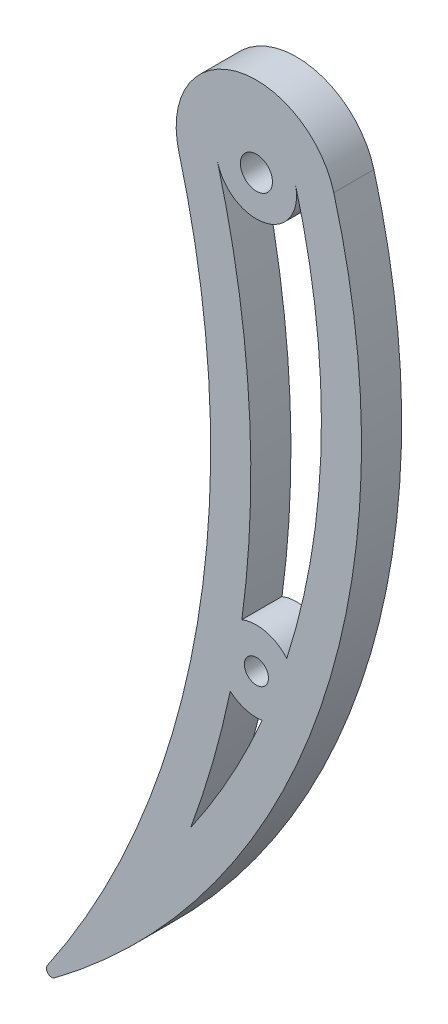
SolidWorks part; units mm, degrees
material "1060 Alloy"
ref_plane "Front Plane" through (0, 0, 0) normal (0, 0, 1) x (1, 0, 0)
ref_plane "Top Plane" through (0, 0, 0) normal (0, 1, 0) x (1, 0, 0)
ref_plane "Right Plane" through (0, 0, 0) normal (1, 0, 0) x (0, 0, -1)
sketch "Sketch1" plane through (0, 0, 0) normal (0, 0, 1) x (1, 0, 0)
  line L0 (5.1445, 48.6362) -> (5.1445, -5.1638)
  line L1 (-21.7555, -51.7438) -> (5.1445, -5.1638)
  line L2 (-17.4256, -54.2443) -> (10.1445, -6.5038)
  line L3 (0.1445, 48.6362) -> (0.1445, -5.1638)
  line L4 (10.1445, 48.6362) -> (10.1445, -5.1638)
  line L5 (10.1445, 48.6362) -> (10.1445, -6.5038)
  line L6 (-26.0853, -49.2433) -> (0.1445, -3.8237)
  line L7 (0.1445, 48.6362) -> (0.1445, -3.8237)
  circle A0 centre (5.1445, 48.6362) radius 2
  circle A1 centre (-21.7555, -51.7438) radius 2
  arc A2 (-17.4256, -54.2443) -> (-26.0853, -49.2433) centre (-21.7555, -51.7438) cw
  arc A3 (0.1445, 48.6362) -> (10.1445, 48.6362) centre (5.1445, 48.6362) cw
  circle A4 centre (5.1445, -5.1638) radius 1.5
  arc A5 (10.1445, 48.6362) -> (0.1445, 48.6362) centre (5.1445, 48.6362) ccw
  circle A6 centre (-95.2141, 21.7362) radius 99.0802
  arc A7 (0.1445, -5.1638) -> (10.1445, -5.1638) centre (5.1445, -5.1638) ccw
  circle A8 centre (5.9967, -2.4738) radius 104.0661
  circle A9 centre (-95.2141, 21.7362) radius 108.8802
  dimension "D2" = 4
  dimension "D3" = 4
  dimension "D1" = 3
extrude "Extrude1" add sketch "Sketch1" along normal blind 5 contours A7 L3 L6 A2 L2 A1 | A2 A9 L2 | L5 A9 A3 L4 | A3 A9 A6 A7 A4 A0 L4 | L2 A9 A7 | A7 A9 L5 region at (6.16, 21.4167, 0) region at (-9.5246, -32.956, 0) region at (-2.7557, -31.6611, 0) region at (9.716, -7.2082, 0) region at (10.1257, -5.6796, 0) region at (11.555, 21.7384, 0)
sketch "Sketch3" plane through (0, 0, 0) normal (0, 0, -1) x (-1, 0, 0)
  circle A0 centre (-5.1445, -5.1638) radius 7.5 construction
  arc A1 (4.5159, 46.0523) -> (-14.7839, 51.2976) centre (-5.1445, 48.6362) ccw
  arc A2 (19.9834, -50.8165) -> (-14.7839, 51.2976) centre (77.6238, 25.7843) cw
  circle A3 centre (21.7555, -51.7438) radius 2 construction
  arc A4 (20.9096, -49.9314) -> (4.5159, 46.0523) centre (117.2126, 15.9087) cw
  arc A5 (19.9834, -50.8165) -> (20.9096, -49.9314) centre (20.3737, -50.2978) ccw
  arc M1 (-9.8312, 50.3783) -> (18.5686, -55.5965) centre (95.2141, 21.7362) ccw
  arc M2 (18.5686, -55.5965) -> (26.0853, -49.2433) centre (21.7555, -51.7438) ccw
  arc M3 (26.0853, -49.2433) -> (-0.1445, 48.6362) centre (95.2141, 21.7362) cw
  arc M4 (-0.1445, 48.6362) -> (-9.8312, 50.3783) centre (-5.1445, 48.6362) ccw
  circle M5 centre (21.7555, -51.7438) radius 2
  dimension "D1" = 15
  dimension "D2" = 20
extrude "Cut-Extrude1" cut sketch "Sketch3" against normal blind 10 contours A4 A2 M5 M1 M2 M3 region at (-15.9387, -38.3925, 0)
extrude "Boss-Extrude1" add sketch "Sketch3<3>" against normal blind 5 contours A4 A1 A2 M3 M1 M4 | A5 M5 region at (0.2001, 9.8384, 0) region at (-20.5766, -50.5101, 0)
sketch "Sketch3<3>" plane through (0, 0, 0) normal (0, 0, -1) x (-1, 0, 0) same geometry as "Sketch3"
sketch "Sketch4" plane through (0, 0, 0) normal (0, 0, -1) x (-1, 0, 0)
  arc A5 (-5.8494, -10.1138) -> (-1.879, -8.9501) centre (-5.1445, -5.1638) ccw
  arc A6 (-9.9642, 49.9669) -> (-0.363, 50.0981) centre (-5.1445, 48.6362) ccw
  arc A7 (-3.3338, -0.5032) -> (-8.9242, -1.8905) centre (-5.1445, -5.1638) ccw
  arc A8 (-1.879, -8.9501) -> (3.0469, -26.1266) centre (117.2126, 15.9087) ccw
  arc A9 (-5.8494, -10.1138) -> (3.0469, -26.1266) centre (77.6238, 25.7843) ccw
  arc A10 (-0.3143, 47.3443) -> (3.0469, -26.1266) centre (117.2126, 15.9087) ccw
  arc A11 (-0.3143, 47.3443) -> (-9.9642, 49.9669) centre (-5.1445, 48.6362) ccw
  arc A12 (-9.9642, 49.9669) -> (3.0469, -26.1266) centre (77.6238, 25.7843) ccw
  arc A13 (-0.3143, 47.3443) -> (-3.3338, -0.5032) centre (117.2126, 15.9087) ccw
  arc A14 (-0.3143, 47.3443) -> (-0.363, 50.0981) centre (-5.1445, 48.6362) ccw
  arc A15 (-9.9642, 49.9669) -> (-8.9242, -1.8905) centre (77.6238, 25.7843) ccw
  dimension "D2" = 5
  dimension "D1" = 5
extrude "Cut-Extrude2" cut sketch "Sketch4" against normal blind 5 contours A6 A15 A7 A13 | A5 A9 A8 region at (1.6968, -15.4545, 0) region at (7.9618, 23.9826, 0)
move or copy body "Body-Move/Copy1" [suppressed] bodies to move or copy 106
move or copy body "Body-Move/Copy2" [suppressed] bodies to move or copy 106
